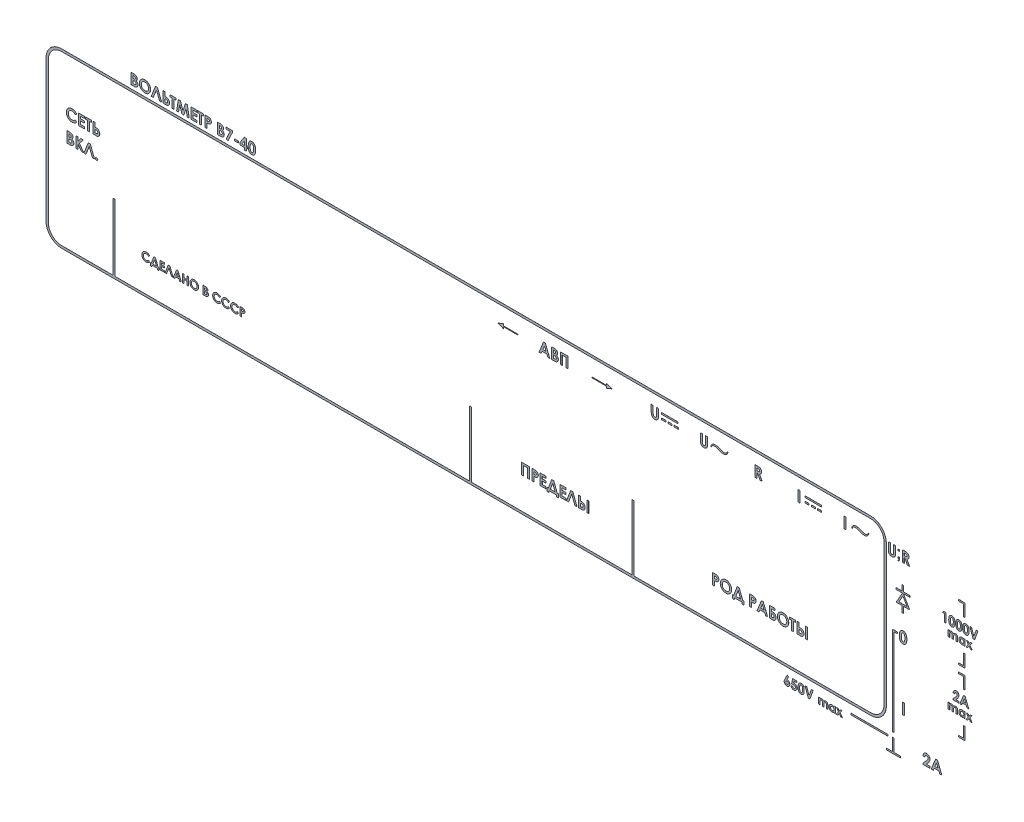
SolidWorks part; units mm, degrees
ref_plane "Спереди" through (0, 0, 0) normal (0, 0, 1) x (1, 0, 0)
ref_plane "Сверху" through (0, 0, 0) normal (0, 1, 0) x (1, 0, 0)
ref_plane "Справа" through (0, 0, 0) normal (1, 0, 0) x (0, 0, -1)
sketch "Эскиз1" plane through (0, 0, 0) normal (0, 0, 1) x (1, 0, 0)
  line L0 (-150, -35) -> (150, -35) construction
  line L1 (-150, 35) -> (150, 35) construction
  line L2 (-5.5, -5.5) -> (-5.5, 5.5) construction
  line L3 (-12.25, -26.25) -> (-11.5, -26.25)
  line L4 (-12.25, -26.25) -> (-12.25, -5.5)
  line L5 (-12.25, -5.5) -> (-11.5, -5.5)
  line L6 (-142, 28) -> (115.5, 28)
  line L7 (-147, 23) -> (-147, -22)
  line L8 (-142, -27) -> (115.5, -27)
  line L9 (120.5, 23) -> (120.5, -22)
  line L10 (-150, 35) -> (-150, -35) construction
  line L11 (-11.5, -26.25) -> (-11.5, -5.5)
  line L12 (115.5, 5.5) -> (115.5, -5.5) construction
  line L13 (-146.25, 23) -> (-146.25, -22)
  line L14 (-142, -26.25) -> (115.5, -26.25)
  line L15 (119.75, 23) -> (119.75, -22)
  line L16 (-142, 27.25) -> (115.5, 27.25)
  line L18 (40.25, -26.25) -> (40.25, -5.5)
  line L19 (39.5, -26.25) -> (40.25, -26.25)
  line L20 (39.5, -5.5) -> (40.25, -5.5)
  line L21 (39.5, -26.25) -> (39.5, -5.5)
  line L22 (35.5, -5.5) -> (35.5, 5.5) construction
  line L25 (44.5, -5.5) -> (55.5, -5.5) construction
  line L26 (-125.75, -26.25) -> (-125.75, -5)
  line L27 (-125, -26.25) -> (-125, -5)
  line L28 (-125.75, -26.25) -> (-125, -26.25)
  line L29 (-125.75, -5) -> (-125, -5)
  line L30 (-120, 25) -> (-120, -5) construction
  line L31 (-120, -5) -> (-20, -5) construction
  line L32 (-5.5, -5.5) -> (5.5, -5.5) construction
  arc A0 (-142, 28) -> (-147, 23) centre (-142, 23) ccw
  arc A1 (-147, -22) -> (-142, -27) centre (-142, -22) ccw
  arc A2 (115.5, -27) -> (120.5, -22) centre (115.5, -22) ccw
  arc A3 (115.5, 28) -> (120.5, 23) centre (115.5, 23) cw
  arc A4 (-146.25, -22) -> (-142, -26.25) centre (-142, -22) ccw
  arc A5 (115.5, -26.25) -> (119.75, -22) centre (115.5, -22) ccw
  arc A6 (115.5, 27.25) -> (119.75, 23) centre (115.5, 23) cw
  arc A7 (-142, 27.25) -> (-146.25, 23) centre (-142, 23) ccw
  dimension "D7" = 5
  dimension "D2" = 0.75
  dimension "D3" = 8
  dimension "D4" = 7
  dimension "D5" = 3
  dimension "D6" = 5
  dimension "D9" = 6
  dimension "D11" = 0.75
  dimension "D12" = 4
  dimension "D13" = 0.75
  dimension "D14" = 5
  dimension "D8" = 0.75
extrude "Рамка" add sketch "Эскиз1" along normal blind 0.01 contours A3 L6 A0 L7 A1 L8 A2 L9 A7 L16 A6 L15 A5 L14 L3 A4 L13 | L3 L11 L5 L4 | L21 L14 L18 L20 | L29 L26 L14 L27 region at (-11.875, -15.875, 0) region at (-125.375, -15.625, 0) region at (39.875, -15.875, 0) region at (-13.25, 27.7269, 0)
sketch "Эскиз2" plane through (0, 0, 0) normal (0, 0, 1) x (1, 0, 0)
  line L0 (-11.5, -26.25) -> (39.5, -26.25) construction
  line L1 (40.25, -26.25) -> (115.5, -26.25) construction
  line L2 (-146.25, 23) -> (-146.25, -22) construction
  line L3 (15, 15) -> (15, 25.3677) construction
  line L4 (26.8009, 21.9535) -> (26.8009, 21.7035)
  line L5 (-3.1106, 21.8383) -> (-1.3606, 22.5785)
  line L6 (31.3606, 21.9535) -> (31.3606, 22.5785)
  line L7 (31.3606, 21.7035) -> (26.8009, 21.7035)
  line L8 (31.3606, 21.7035) -> (31.3606, 21.0785)
  line L9 (31.3606, 21.0785) -> (33.1106, 21.8383)
  line L10 (31.3606, 21.9535) -> (26.8009, 21.9535)
  line L11 (-1.3606, 21.9535) -> (3.1991, 21.9535)
  line L12 (-1.3606, 21.0785) -> (-3.1106, 21.8383)
  line L13 (-1.3606, 21.7035) -> (-1.3606, 21.0785)
  line L14 (-1.3606, 21.7035) -> (3.1991, 21.7035)
  line L15 (-1.3606, 21.9535) -> (-1.3606, 22.5785)
  line L16 (3.1991, 21.9535) -> (3.1991, 21.7035)
  line L17 (33.1106, 21.8383) -> (31.3606, 22.5785)
  line L18 (-142, 27.25) -> (115.5, 27.25) construction
  line L19 (49.0078, 23.23) -> (54.2578, 23.23)
  line L20 (49.0078, 23.23) -> (49.0078, 22.73)
  line L21 (49.0078, 22.73) -> (54.2578, 22.73)
  line L22 (54.2578, 23.23) -> (54.2578, 22.73)
  line L23 (49.0078, 21.73) -> (50.3078, 21.73)
  line L24 (49.0078, 21.73) -> (49.0078, 21.23)
  line L25 (49.0078, 21.23) -> (50.3078, 21.23)
  line L26 (50.3078, 21.73) -> (50.3078, 21.23)
  line L27 (50.9878, 21.73) -> (52.2878, 21.73)
  line L28 (50.9878, 21.73) -> (50.9878, 21.23)
  line L29 (50.9878, 21.23) -> (52.2878, 21.23)
  line L30 (52.2878, 21.73) -> (52.2878, 21.23)
  line L31 (52.9678, 21.73) -> (54.2678, 21.73)
  line L32 (52.9678, 21.73) -> (52.9678, 21.23)
  line L33 (52.9678, 21.23) -> (54.2678, 21.23)
  line L34 (54.2678, 21.73) -> (54.2678, 21.23)
  line L35 (99.9003, 21.613) -> (99.9003, 21.113)
  line L36 (99.8903, 23.113) -> (99.8903, 22.613)
  line L37 (96.6203, 21.613) -> (96.6203, 21.113)
  line L38 (94.6403, 21.113) -> (95.9403, 21.113)
  line L39 (94.6403, 21.613) -> (94.6403, 21.113)
  line L40 (98.6003, 21.113) -> (99.9003, 21.113)
  line L41 (94.6403, 22.613) -> (99.8903, 22.613)
  line L42 (98.6003, 21.613) -> (99.9003, 21.613)
  line L43 (94.6403, 23.113) -> (94.6403, 22.613)
  line L44 (96.6203, 21.613) -> (97.9203, 21.613)
  line L45 (94.6403, 21.613) -> (95.9403, 21.613)
  line L46 (96.6203, 21.113) -> (97.9203, 21.113)
  line L47 (95.9403, 21.613) -> (95.9403, 21.113)
  line L48 (94.6403, 23.113) -> (99.8903, 23.113)
  line L49 (98.6003, 21.613) -> (98.6003, 21.113)
  line L50 (97.9203, 21.613) -> (97.9203, 21.113)
  line L51 (122.5, -33.5) -> (120.5, -33.5)
  line L52 (122.5, -29.5) -> (123, -29.5)
  line L53 (122.5, -29.5) -> (122.5, -33.5)
  line L54 (-150, -35) -> (150, -35) construction
  line L55 (123, -29.5) -> (123, -33.5)
  line L56 (125, -33.5) -> (123, -33.5)
  line L57 (125, -33.5) -> (125, -34)
  line L58 (125, -34) -> (120.5, -34)
  line L59 (120.5, -33.5) -> (120.5, -34)
  line L60 (120.5, 23) -> (120.5, -22) construction
  text T0 "ПРЕДЕЛЫ" font "Century Gothic" height 3.5
  text T1 "РОД РАБОТЫ\r\n" font "Century Gothic" height 3.5
  text T2 "СЕТЬ\r\nВКЛ." font "Century Gothic" height 3.5
  text T3 "АВП" font "Century Gothic" height 3.5
  text T4 "U" font "Century Gothic" height 3.5
  text T5 "U" font "Century Gothic" height 3.5
  text T6 "~" font "Symbol" height 5.25
  text T7 "R" font "Century Gothic" height 3.5
  text T8 "I" font "Century Gothic" height 3.5
  text T9 "I" font "Century Gothic" height 3.5
  text T10 "~" font "Symbol" height 5.25
  text T11 "U R" font "Century Gothic" height 3.5
  text T12 ";" font "Microsoft Sans Serif" height 3.5
  text T13 "0" font "Century Gothic" height 3.5
  text T14 "I" font "Century Gothic" height 3.5
  text T15 "2A" font "Century Gothic" height 3.5
  dimension "D18" = 5.36
  dimension "D22" = 0.5
  dimension "D1" = 10
  dimension "D2" = 10
  dimension "D3" = 5.5
  dimension "D4" = 5.25
  dimension "D5" = 0.5
  dimension "D6" = 0.5
  dimension "D7" = 0.5
  dimension "D8" = 0.5
  dimension "D9" = 1.3
  dimension "D10" = 1.3
  dimension "D11" = 1.3
  dimension "D12" = 0.68
  dimension "D13" = 0.68
  dimension "D14" = 6.89
  dimension "D15" = 4.02
  dimension "D16" = 6.8911
  dimension "D17" = 5.52
  dimension "D19" = 5.36
  dimension "D20" = 3.7426
  dimension "D21" = 5.25
  dimension "D23" = 0.5
  dimension "D24" = 0.5
  dimension "D25" = 0.5
  dimension "D26" = 1.3
  dimension "D27" = 1.3
  dimension "D28" = 1.3
  dimension "D29" = 0.68
  dimension "D30" = 0.68
  dimension "D31" = 2.5
  dimension "D32" = 5.243
  dimension "D33" = 5.243
  dimension "D34" = 5.24
  dimension "D35" = 2.5
  dimension "D36" = 2
  dimension "D37" = 2
  dimension "D38" = 0.5
  dimension "D39" = 0.5
  dimension "D40" = 4
  dimension "D41" = 1
  dimension "D42" = 2
extrude "Текст на панели" add sketch "Эскиз2" along normal blind 0.01 separate body
sketch "Надпись \"Вольтметр\"" plane through (0, 0, 0) normal (0, 0, 1) x (1, 0, 0)
  text T0 "ВОЛЬТМЕТР В7-40" font "Century Gothic" height in points 13
  text T1 "СДЕЛАНО В СССР" font "Century Gothic" height in points 10
extrude "Текст \"Вольметр\"" add sketch "Надпись \"Вольтметр\"" along normal blind 0.01 separate body
sketch "Эскиз5" plane through (0, 0, 0) normal (0, 0, 1) x (1, 0, 0)
  line L0 (135, 10) -> (124.9574, 10) construction
  line L1 (127.0921, 8.789) -> (125.7931, 11.039)
  line L2 (126.0431, 6.3161) -> (125.5431, 6.3161)
  line L3 (126.0431, 6.3161) -> (126.0431, 8.8319)
  line L4 (126.0431, 14.039) -> (125.5431, 14.039)
  line L5 (125.5431, 6.3161) -> (125.5431, 8.8319)
  line L6 (126.0431, 6.3161) -> (125.8826, 8.7944) construction
  line L7 (126.0431, 14.039) -> (125.8432, 10.9521) construction
  line L8 (125.7931, 12.039) -> (123.628, 8.289)
  line L9 (123.628, 8.289) -> (127.9582, 8.289)
  line L10 (127.9582, 8.289) -> (125.7931, 12.039)
  line L11 (125.7931, 11.039) -> (124.4941, 8.789)
  line L12 (124.4941, 8.789) -> (127.0921, 8.789)
  line L13 (125.7931, 13.4286) -> (125.7931, 11.039) construction
  line L14 (123.6281, 11.789) -> (127.9581, 11.789)
  line L15 (123.6281, 11.789) -> (123.6281, 12.289)
  line L16 (123.6281, 12.289) -> (127.9581, 12.289)
  line L17 (127.9581, 11.789) -> (127.9581, 12.289)
  line L18 (123.6281, 11.789) -> (127.9581, 12.289) construction
  line L19 (123.6281, 12.289) -> (127.9581, 11.789) construction
  line L20 (126.0431, 10.606) -> (126.0431, 14.039)
  line L21 (125.7931, 10.1776) -> (125.7816, 10) construction
  line L22 (125.7931, 10.1776) -> (125.7931, 10) construction
  line L23 (125.7429, 10.9521) -> (125.5431, 14.039) construction
  line L24 (125.5431, 10.606) -> (125.5431, 14.039)
  line L25 (125.7035, 8.7944) -> (125.5431, 6.3161) construction
  line L26 (125.7931, 8.789) -> (125.7931, 6.4131) construction
  line L27 (125.8046, 10) -> (125.7931, 10.1776) construction
  circle A0 centre (125.7931, 9.539) radius 0.75 construction
  point P2 (125.7931, 9.339)
  dimension "D4" = 1.5
  dimension "D2" = 0.75
  dimension "D1" = 0.5
  dimension "D5" = 0.5
  dimension "D6" = 4.33
  dimension "D7" = 2
  dimension "D8" = 1.9729
  dimension "D9" = 1.039
  dimension "D10" = 0.5
  dimension "D3" = 0.5
extrude "Бобышка-Вытянуть2" add sketch "Эскиз5" along normal blind 0.01 separate body contours L12 L3 L9 L10 L1 | L14 L8 L5 L11 L1 L3 L10 | L8 L14 L10 | L16 L15 L14 L5 | L16 L5 L14 L8 L10 L3 | L5 L16 L3 L4 | L14 L17 L16 L3 | L12 L11 L5 L8 L9 | L12 L5 L9 L3 | L9 L5 L2 L3 region at (126.8052, 9.3947, 0) region at (125.7931, 11.2797, 0) region at (125.7931, 8.539, 0) region at (125.7931, 7.3026, 0) region at (124.781, 9.3947, 0) region at (125.7931, 11.8723, 0) region at (125.7931, 12.0671, 0) region at (127.0006, 12.039, 0) region at (125.7931, 13.164, 0) region at (124.5856, 12.039, 0)
sketch "Красные линии" plane through (0, 0, 0) normal (0, 0, 1) x (1, 0, 0)
  line L0 (120.5, 23) -> (120.5, -22) construction
  line L1 (109.3171, -29.5) -> (121, -29.5)
  line L2 (109.3171, -29.5) -> (109.3171, -30)
  line L3 (109.3171, -30) -> (121, -30)
  line L4 (121, -29.5) -> (121, -30)
  line L5 (122.5, -28) -> (123, -28)
  line L6 (122.5, -28) -> (122.5, 0.25)
  line L7 (122.5, 0.25) -> (123, 0.25)
  line L8 (123, -28) -> (123, -0.25)
  line L9 (122.5, 0.25) -> (124, 0.25)
  line L10 (122.5, 0.25) -> (122.5, -0.5)
  line L11 (123, -0.25) -> (124, -0.25)
  line L12 (124, 0.25) -> (124, -0.25)
  line L13 (123, -29.5) -> (122.5, -29.5) construction
  line L14 (147.0145, -10) -> (126.8467, -10) construction
  line L15 (122.5, -29.5) -> (122.5, -33.5) construction
  line L16 (147.965, 0) -> (188.2825, 0) construction
  line L17 (143.5, -1.5) -> (145, -1.5)
  line L18 (143.5, -1.5) -> (143.5, -1)
  line L19 (143.5, -1) -> (145.5, -1)
  line L20 (145.5, -1.2804) -> (145.5, -1)
  line L21 (145.5, -1) -> (145, -1)
  line L22 (145.5, -1) -> (145.5, -5)
  line L23 (145.5, -5) -> (145, -5)
  line L24 (145, -1.5) -> (145, -5)
  line L25 (135, 10) -> (147.0145, 10) construction
  line L26 (145, -18.5) -> (145, -15)
  line L27 (145.5, -15) -> (145, -15)
  line L28 (145.5, -19) -> (145.5, -15)
  line L29 (145.5, -19) -> (145, -19)
  line L30 (145.5, -18.7196) -> (145.5, -19)
  line L31 (143.5, -19) -> (145.5, -19)
  line L32 (143.5, -18.5) -> (143.5, -19)
  line L33 (143.5, -18.5) -> (145, -18.5)
  line L34 (147.965, 0) -> (163.6779, 0) construction
  line L35 (143.5, 18.5) -> (145, 18.5)
  line L36 (143.5, 18.5) -> (143.5, 19)
  line L37 (143.5, 19) -> (145.5, 19)
  line L38 (145.5, 18.7196) -> (145.5, 19)
  line L39 (145.5, 19) -> (145, 19)
  line L40 (145.5, 19) -> (145.5, 15)
  line L41 (145.5, 15) -> (145, 15)
  line L42 (145, 18.5) -> (145, 15)
  line L43 (145, 1.5) -> (145, 5)
  line L44 (145.5, 5) -> (145, 5)
  line L45 (145.5, 1) -> (145.5, 5)
  line L46 (145.5, 1) -> (145, 1)
  line L47 (145.5, 1.2804) -> (145.5, 1)
  line L48 (143.5, 1) -> (145.5, 1)
  line L49 (143.5, 1.5) -> (143.5, 1)
  line L50 (143.5, 1.5) -> (145, 1.5)
  circle A0 centre (135, 0) radius 7 construction
  dimension "D1" = 2
  dimension "D2" = 0.5
  dimension "D3" = 0.5
  dimension "D4" = 1
  dimension "D5" = 0.5
  dimension "D6" = 0.25
  dimension "D7" = 1.5
  dimension "D8" = 1.5
  dimension "D9" = 0.5
  dimension "D10" = 8.5
  dimension "D11" = 2
  dimension "D12" = 0.5
  dimension "D13" = 4
  dimension "D14" = 1
  dimension "D15" = 10
extrude "Бобышка-Вытянуть3" add sketch "Красные линии" along normal blind 0.01 separate body contours L1 L4 L3 L2 | L6 L5 L8 L11 L12 L9 | L31 L32 L33 L26 L27 L28 | L22 L23 L24 L17 L18 L19 | L45 L44 L43 L50 L49 L48 | L40 L41 L42 L35 L36 L37
sketch "Красные надписи" plane through (0, 0, 0) normal (0, 0, 1) x (1, 0, 0)
  text T0 "1000V" font "Century Gothic" height in points 11
  text T1 "max" font "Century Gothic" height in points 10
  text T2 "2A" font "Century Gothic" height in points 11
  text T3 "max" font "Century Gothic" height in points 10
  text T4 "650V" font "Century Gothic" height in points 11
  text T5 "max" font "Century Gothic" height in points 10
  dimension "D1" = 9.5909
  dimension "D2" = 9.59
  dimension "D3" = 3.3447
  dimension "D4" = 3.34
extrude "Бобышка-Вытянуть4" add sketch "Красные надписи" along normal blind 0.01 separate body
